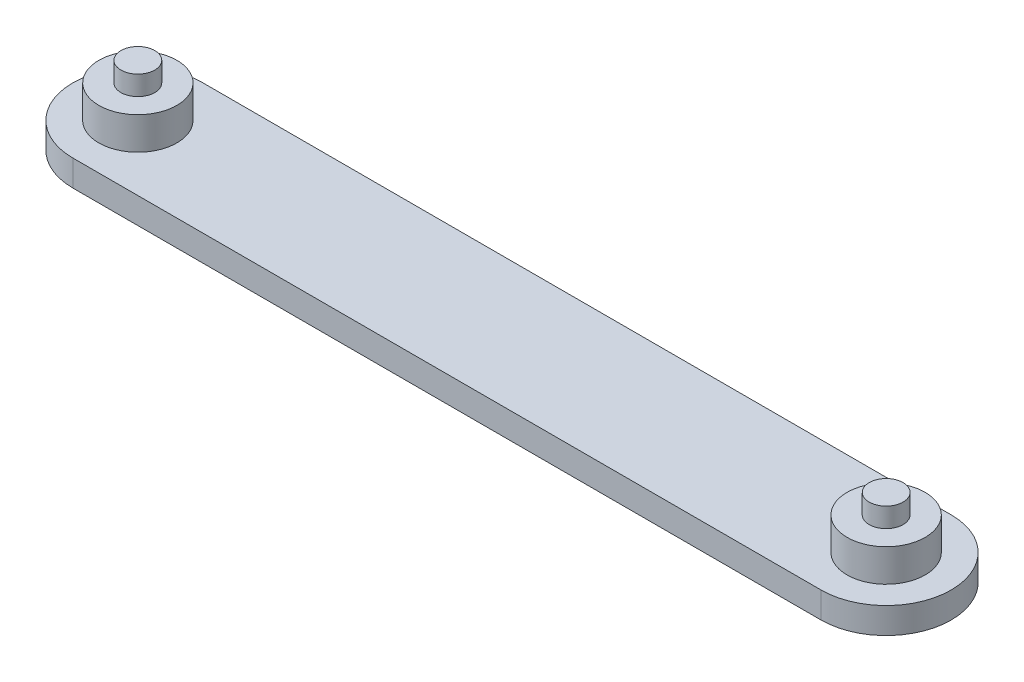
SolidWorks part; units mm, degrees
ref_plane "Front Plane" through (0, 0, 0) normal (0, 0, 1) x (1, 0, 0)
ref_plane "Top Plane" through (0, 0, 0) normal (0, 1, 0) x (1, 0, 0)
ref_plane "Right Plane" through (0, 0, 0) normal (1, 0, 0) x (0, 0, -1)
sketch "Sketch1" plane through (0, 0, 0) normal (0, 1, 0) x (1, 0, 0)
  line L1 (0, 0) -> (67.5, 0)
  line L2 (0, 0) -> (0, 10)
  line L3 (0, 10) -> (67.5, 10)
  line L4 (67.5, 0) -> (67.5, 10)
  dimension "D1" = 10
  dimension "D2" = 67.5
extrude "Boss-Extrude4" add sketch "Sketch1" along normal blind 2
sketch "Sketch4" plane through (0, 2, 0) normal (0, 1, 0) x (1, 0, 0)
  line L0 (33.75, 10) -> (33.75, 0) construction
  line L1 (67.5, 10) -> (0, 10) construction
  line L2 (0, 0) -> (67.5, 0) construction
  circle A0 centre (5, 5) radius 3.5
  circle A1 centre (62.5, 5) radius 3.5
  dimension "D1" = 5
  dimension "D3" = 7
  dimension "D2" = 5
extrude "Boss-Extrude6" add sketch "Sketch4" along normal blind 2.5
sketch "Sketch5" plane through (0, 2, 0) normal (0, 1, 0) x (1, 0, 0)
  line L0 (62.5, 10) -> (67.5, 10)
  line L1 (0, 10) -> (5, 10)
  line L2 (0, 10) -> (0, 0)
  line L3 (0, 0) -> (5, 0)
  line L4 (67.5, 10) -> (67.5, 0)
  line L5 (62.5, 0) -> (67.5, 0)
  arc A0 (5, 10) -> (5, 0) centre (5, 5) ccw
  arc A1 (62.5, 0) -> (62.5, 10) centre (62.5, 5) ccw
  line M4 (0, 10) -> (0, 0)
  line M5 (0, 0) -> (67.5, 0)
  line M6 (67.5, 0) -> (67.5, 10)
  line M7 (67.5, 10) -> (0, 10)
  dimension "D1" = 10
  dimension "D2" = 10
extrude "Cut-Extrude2" cut sketch "Sketch5" against normal blind 2.5 contours A0 L2 M5 | A0 M7 M4 | A1 L4 M7 | A1 M5 M6 | L1 A0 L3 L2 region at (66.3832, 2, -8.8832) region at (66.3832, 2, -1.1168) region at (1.1168, 2, -8.8832) region at (1.1168, 2, -1.1168)
sketch "Sketch7" plane through (0, 4.5, 0) normal (0, 1, 0) x (1, 0, 0)
  circle A0 centre (5, 5) radius 3
  circle A1 centre (62.5, 5) radius 3
  circle A2 centre (5, 5) radius 3.5
  circle A3 centre (62.5, 5) radius 3.5
  dimension "D1" = 6
  dimension "D2" = 6
extrude "Cut-Extrude3" cut sketch "Sketch7" against normal blind 2.5
sketch "Sketch8" plane through (0, 4.5, 0) normal (0, 1, 0) x (1, 0, 0)
  circle A0 centre (5, 5) radius 1.3
  circle A1 centre (62.5, 5) radius 1.3
  dimension "D1" = 2.6
  dimension "D2" = 2.6
extrude "Boss-Extrude7" add sketch "Sketch8" along normal blind 1.5
